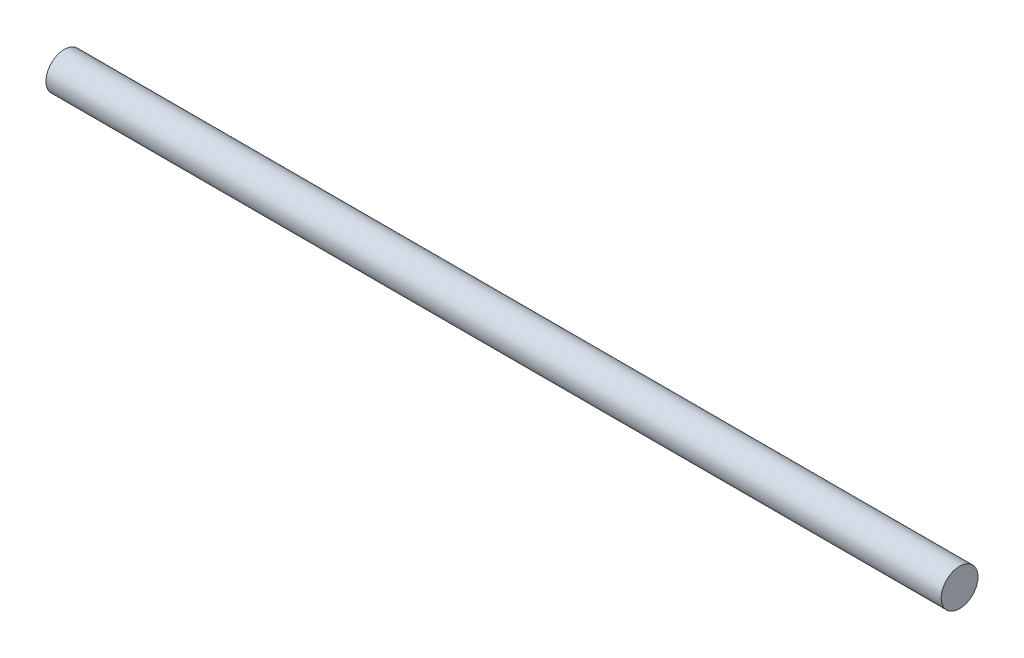
SolidWorks part; units mm, degrees
material "普通碳钢"
ref_plane "前视基准面" through (0, 0, 0) normal (0, 0, 1) x (1, 0, 0)
ref_plane "上视基准面" through (0, 0, 0) normal (0, 1, 0) x (1, 0, 0)
ref_plane "右视基准面" through (0, 0, 0) normal (1, 0, 0) x (0, 0, -1)
sketch "草图1" plane through (0, 0, 0) normal (1, 0, 0) x (0, 0, -1)
  circle A0 centre (0, 0) radius 3
  dimension "D1" = 6
extrude "凸台-拉伸1" add sketch "草图1" along normal blind 146
cosmetic thread "装饰螺纹线1" parameters "D2"=4.917
